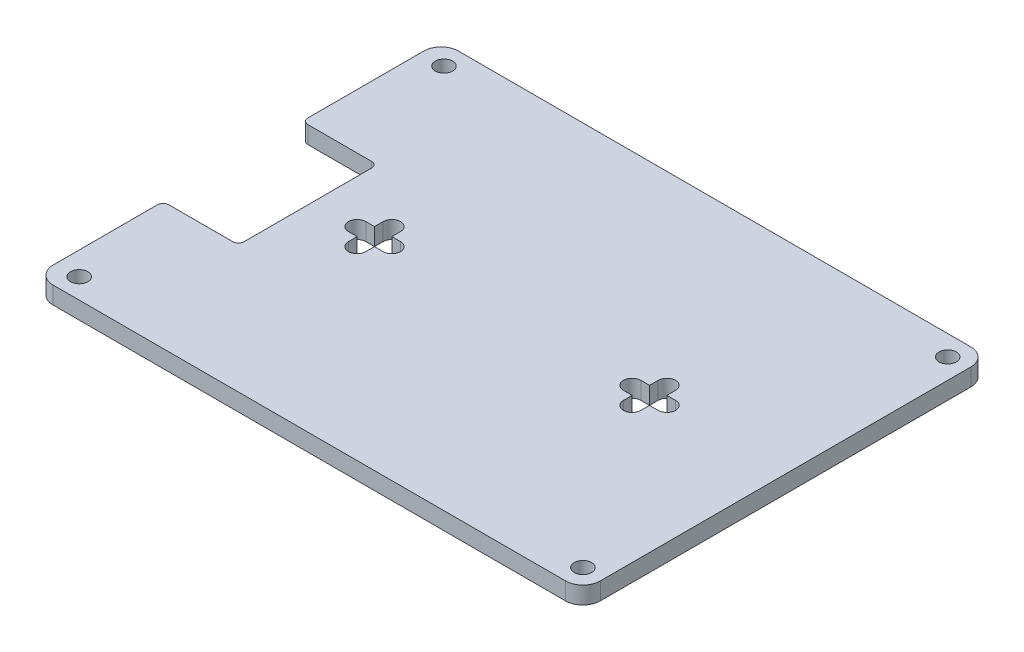
SolidWorks part; units mm, degrees
material "Acrylic (Medium-high impact)"
ref_plane "Front Plane" through (0, 0, 0) normal (0, 0, 1) x (1, 0, 0)
ref_plane "Top Plane" through (0, 0, 0) normal (0, 1, 0) x (1, 0, 0)
ref_plane "Right Plane" through (0, 0, 0) normal (1, 0, 0) x (0, 0, -1)
sketch "Sketch1" plane through (0, 0, 0) normal (0, 1, 0) x (1, 0, 0)
  line L1 (-47.25, 35) -> (47.25, 35)
  line L2 (-47.25, 35) -> (-47.25, -35)
  line L3 (-47.25, -35) -> (47.25, -35)
  line L4 (47.25, 35) -> (47.25, -35)
  line L5 (-47.25, 35) -> (47.25, -35) construction
  line L6 (-47.25, -35) -> (47.25, 35) construction
  point P0 (0, 0)
  dimension "D1" = 70
  dimension "D2" = 94.5
extrude "Boss-Extrude1" add sketch "Sketch1" along normal blind 3
sketch "Sketch3" plane through (0, 3, 0) normal (0, 1, 0) x (1, 0, 0)
  line L0 (47.25, -35) -> (47.25, 35) construction
  line L2 (47.25, 35) -> (-47.25, 35) construction
  circle A0 centre (43.75, 31.5) radius 1.5
  circle A1 centre (-43.25, 31.5) radius 1.5
  circle A2 centre (-43.25, -31.5) radius 1.5
  circle A3 centre (43.75, -31.5) radius 1.5
  dimension "D1" = 3
  dimension "D2" = 3.5
  dimension "D3" = 3.5
  dimension "D4" = 2
  dimension "D5" = 87
  dimension "D6" = 63
  dimension "D7" = 2
extrude "Cut-Extrude2" cut sketch "Sketch3" against normal through all
fillet "Fillet2" radius 3 4 edges at (-47.25, 1.5, 35) (-47.25, 1.5, -35) (47.25, 1.5, -35) (47.25, 1.5, 35)
sketch "Sketch5" plane through (0, 3, 0) normal (0, 1, 0) x (1, 0, 0)
  line L5 (0, 18.3176) -> (0, -15.9274) construction
  line L17 (44.25, 35) -> (-44.25, 35) construction
  line L18 (-47.25, 32) -> (-47.25, -32) construction
  line L19 (-47.25, 11) -> (-47.25, -13)
  line L20 (-25.25, 4.5) -> (-22.25, 4.5)
  line L21 (-22.25, 4.5) -> (-22.25, 1.5)
  line L22 (25.25, 1.5) -> (25.25, 4.5)
  line L23 (-22.25, 1.5) -> (-19.25, 1.5)
  line L24 (-19.25, 1.5) -> (-19.25, -1.5)
  line L25 (-19.25, -1.5) -> (-22.25, -1.5)
  line L26 (-22.25, -1.5) -> (-22.25, -4.5)
  line L27 (-47.25, 11) -> (-34.25, 11)
  line L28 (-34.25, 11) -> (-34.25, -13)
  line L29 (-34.25, -13) -> (-47.25, -13)
  line L30 (-22.25, -4.5) -> (-25.25, -4.5)
  line L31 (-25.25, -4.5) -> (-25.25, -1.5)
  line L32 (-25.25, -1.5) -> (-28.25, -1.5)
  line L33 (-28.25, -1.5) -> (-28.25, 1.5)
  line L34 (-28.25, 1.5) -> (-25.25, 1.5)
  line L35 (-25.25, 1.5) -> (-25.25, 4.5)
  line L36 (28.25, 1.5) -> (25.25, 1.5)
  line L37 (28.25, -1.5) -> (28.25, 1.5)
  line L38 (25.25, -1.5) -> (28.25, -1.5)
  line L39 (25.25, -4.5) -> (25.25, -1.5)
  line L40 (22.25, -4.5) -> (25.25, -4.5)
  line L41 (22.25, -1.5) -> (22.25, -4.5)
  line L42 (19.25, -1.5) -> (22.25, -1.5)
  line L43 (19.25, 1.5) -> (19.25, -1.5)
  line L44 (22.25, 1.5) -> (19.25, 1.5)
  line L45 (22.25, 4.5) -> (22.25, 1.5)
  line L46 (25.25, 4.5) -> (22.25, 4.5)
  point P16 (-19.25, 0)
  point P36 (0, 0)
  line M17 (-47.25, 32) -> (-47.25, -32)
  dimension "D1" = 3
  dimension "D2" = 6
  dimension "D5" = 24
  dimension "D6" = 24
  dimension "D7" = 13
extrude "Cut-Extrude3" cut sketch "Sketch5" against normal through all contours L29 L28 L27 M17 | L35 L34 L33 L32 L31 L30 L26 L25 L24 L23 L21 L20 | L22 L46 L45 L44 L43 L42 L41 L40 L39 L38 L37 L36 region at (-40.75, 3, 1) region at (-23.75, 3, 0) region at (23.75, 3, 0)
fillet "Fillet3" radius 1 4 edges at (-47.25, 1.5, 13) (-47.25, 1.5, -11) (-34.25, 1.5, 13) (-34.25, 1.5, -11)
fillet "Fillet5" 2 edges at (-25.25, 1.5, -4.5) (-22.25, 1.5, -4.5) type full round first side face at (-25.25, 1.5, -3) second side face at (-22.25, 1.5, -3) middle face at (-23.75, 1.5, -4.5)
fillet "Fillet6" 2 edges at (-28.25, 1.5, 1.5) (-28.25, 1.5, -1.5) type full round first side face at (-26.75, 1.5, 1.5) second side face at (-26.75, 1.5, -1.5) middle face at (-28.25, 1.5, 0)
fillet "Fillet7" 2 edges at (-19.25, 1.5, -1.5) (-19.25, 1.5, 1.5) type full round first side face at (-20.75, 1.5, -1.5) second side face at (-20.75, 1.5, 1.5) middle face at (-19.25, 1.5, 0)
fillet "Fillet8" 2 edges at (-22.25, 1.5, 4.5) (-25.25, 1.5, 4.5) type full round first side face at (-22.25, 1.5, 3) second side face at (-25.25, 1.5, 3) middle face at (-23.75, 1.5, 4.5)
fillet "Fillet9" 2 edges at (22.25, 1.5, -4.5) (25.25, 1.5, -4.5) type full round first side face at (22.25, 1.5, -3) second side face at (25.25, 1.5, -3) middle face at (23.75, 1.5, -4.5)
fillet "Fillet10" 2 edges at (28.25, 1.5, -1.5) (28.25, 1.5, 1.5) type full round first side face at (26.75, 1.5, -1.5) second side face at (26.75, 1.5, 1.5) middle face at (28.25, 1.5, 0)
fillet "Fillet11" 2 edges at (25.25, 1.5, 4.5) (22.25, 1.5, 4.5) type full round first side face at (25.25, 1.5, 3) second side face at (22.25, 1.5, 3) middle face at (23.75, 1.5, 4.5)
fillet "Fillet12" 2 edges at (19.25, 1.5, 1.5) (19.25, 1.5, -1.5) type full round first side face at (20.75, 1.5, 1.5) second side face at (20.75, 1.5, -1.5) middle face at (19.25, 1.5, 0)
